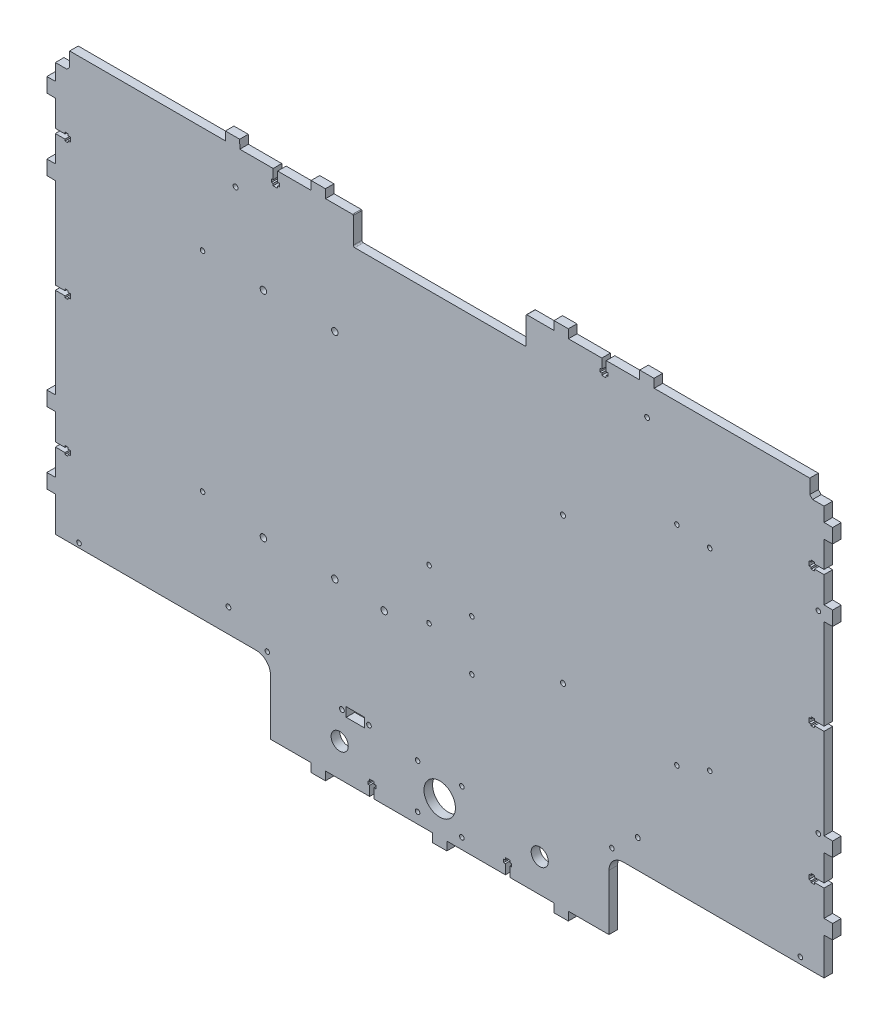
SolidWorks part; units mm, degrees
material "Клен"
ref_plane "Front" through (0, 0, 0) normal (0, 0, 1) x (1, 0, 0)
ref_plane "Top" through (0, 0, 0) normal (0, 1, 0) x (1, 0, 0)
ref_plane "Right" through (0, 0, 0) normal (1, 0, 0) x (0, 0, -1)
sketch "Эскиз1" plane through (0, 0, 0) normal (0, 0, 1) x (1, 0, 0)
  line L0 (89.7419, 500.1376) -> (118.0919, 500.1376)
  line L1 (118.0919, 500.1376) -> (118.1919, 494.1376)
  line L2 (118.1919, 494.1376) -> (128.1919, 494.1376)
  line L3 (128.1919, 494.1376) -> (128.2919, 500.1376)
  line L4 (128.2919, 500.1376) -> (159.1419, 500.1376)
  line L5 (159.1419, 500.1376) -> (159.1419, 506.9376)
  line L6 (159.1419, 506.9376) -> (157.9419, 506.9376)
  line L7 (157.9419, 506.9376) -> (157.9419, 509.1376)
  line L8 (157.9419, 509.1376) -> (159.1419, 509.1376)
  line L9 (159.1419, 509.1376) -> (159.1419, 510.6376)
  line L10 (159.1419, 510.6376) -> (162.2419, 510.6376)
  line L11 (162.2419, 510.6376) -> (162.2419, 509.1376)
  line L12 (162.2419, 509.1376) -> (163.4419, 509.1376)
  line L13 (163.4419, 509.1376) -> (163.4419, 506.9376)
  line L14 (163.4419, 506.9376) -> (162.2419, 506.9376)
  line L15 (162.2419, 506.9376) -> (162.2419, 500.1376)
  line L16 (-51.8081, 695.792) -> (-54.0081, 695.792)
  line L17 (-66.8081, 623.542) -> (-60.8081, 623.442)
  line L18 (162.2419, 500.1376) -> (203.0919, 500.1376)
  line L19 (203.0919, 500.1376) -> (203.1919, 494.1376)
  line L20 (203.1919, 494.1376) -> (213.1919, 494.1376)
  line L21 (213.1919, 494.1376) -> (213.2919, 500.1376)
  line L22 (213.2919, 500.1376) -> (254.1419, 500.1376)
  line L23 (254.1419, 500.1376) -> (254.1419, 506.9376)
  line L24 (254.1419, 506.9376) -> (252.9419, 506.9376)
  line L25 (252.9419, 506.9376) -> (252.9419, 509.1376)
  line L26 (252.9419, 509.1376) -> (254.1419, 509.1376)
  line L27 (254.1419, 509.1376) -> (254.1419, 510.6376)
  line L28 (254.1419, 510.6376) -> (257.2419, 510.6376)
  line L29 (257.2419, 510.6376) -> (257.2419, 509.1376)
  line L30 (257.2419, 509.1376) -> (258.4419, 509.1376)
  line L31 (258.4419, 509.1376) -> (258.4419, 506.9376)
  line L32 (258.4419, 506.9376) -> (257.2419, 506.9376)
  line L33 (257.2419, 506.9376) -> (257.2419, 500.1376)
  line L34 (257.2419, 500.1376) -> (288.0919, 500.1376)
  line L35 (288.0919, 500.1376) -> (288.1919, 494.1376)
  line L36 (288.1919, 494.1376) -> (298.1919, 494.1376)
  line L37 (298.1919, 494.1376) -> (298.2919, 500.1376)
  line L38 (298.2919, 500.1376) -> (326.6419, 500.1376)
  line L97 (367.1919, 847.1376) -> (358.2919, 847.1376)
  line L98 (358.2919, 847.1376) -> (358.1919, 853.1376)
  line L99 (358.1919, 853.1376) -> (348.1919, 853.1376)
  line L100 (348.1919, 853.1376) -> (348.0919, 847.1376)
  line L101 (348.0919, 847.1376) -> (324.7419, 847.1376)
  line L102 (324.7419, 847.1376) -> (324.7419, 840.3376)
  line L103 (324.7419, 840.3376) -> (325.9419, 840.3376)
  line L104 (325.9419, 840.3376) -> (325.9419, 838.1376)
  line L105 (325.9419, 838.1376) -> (324.7419, 838.1376)
  line L106 (324.7419, 838.1376) -> (324.7419, 836.6376)
  line L107 (324.7419, 836.6376) -> (321.6419, 836.6376)
  line L108 (321.6419, 836.6376) -> (321.6419, 838.1376)
  line L109 (321.6419, 838.1376) -> (320.4419, 838.1376)
  line L110 (320.4419, 838.1376) -> (320.4419, 840.3376)
  line L111 (320.4419, 840.3376) -> (321.6419, 840.3376)
  line L112 (321.6419, 840.3376) -> (321.6419, 847.1376)
  line L113 (321.6419, 847.1376) -> (298.2919, 847.1376)
  line L114 (298.2919, 847.1376) -> (298.1919, 853.1376)
  line L115 (298.1919, 853.1376) -> (288.1919, 853.1376)
  line L116 (288.1919, 853.1376) -> (288.0919, 847.1376)
  line L117 (288.0919, 847.1376) -> (269.1919, 847.1376)
  line L118 (268.6919, 846.6376) -> (268.6919, 828.542)
  line L119 (267.6919, 827.542) -> (148.6919, 827.542)
  line L120 (147.6919, 828.542) -> (147.6919, 846.542)
  line L121 (147.1919, 847.042) -> (128.2919, 847.042)
  line L122 (128.2919, 847.042) -> (128.1919, 853.042)
  line L123 (128.1919, 853.042) -> (118.1919, 853.042)
  line L124 (118.1919, 853.042) -> (118.0919, 847.042)
  line L125 (118.0919, 847.042) -> (94.7419, 847.042)
  line L126 (94.7419, 847.042) -> (94.7419, 840.242)
  line L127 (94.7419, 840.242) -> (95.9419, 840.242)
  line L128 (95.9419, 840.242) -> (95.9419, 838.042)
  line L129 (95.9419, 838.042) -> (94.7419, 838.042)
  line L130 (94.7419, 838.042) -> (94.7419, 836.542)
  line L131 (94.7419, 836.542) -> (91.6419, 836.542)
  line L132 (91.6419, 836.542) -> (91.6419, 838.042)
  line L133 (91.6419, 838.042) -> (90.4419, 838.042)
  line L134 (90.4419, 838.042) -> (90.4419, 840.242)
  line L135 (90.4419, 840.242) -> (91.6419, 840.242)
  line L136 (91.6419, 840.242) -> (91.6419, 847.042)
  line L137 (91.6419, 847.042) -> (68.2919, 847.042)
  line L138 (68.2919, 847.042) -> (68.1919, 853.042)
  line L139 (68.1919, 853.042) -> (58.1919, 853.042)
  line L140 (58.1919, 853.042) -> (58.0919, 847.042)
  line L141 (58.0919, 847.042) -> (49.1919, 847.042)
  line L199 (39.1919, 871.432) -> (39.1919, 501.6876) construction
  line L201 (142.7002, 546.3976) -> (155.7002, 546.3976)
  line L202 (155.7002, 546.3976) -> (155.7002, 539.8976)
  line L203 (155.7002, 539.8976) -> (142.7002, 539.8976)
  line L204 (142.7002, 539.8976) -> (142.7002, 546.3976)
  line L205 (-60.8081, 871.432) -> (-60.8081, 501.6876) construction
  line L206 (-50.3081, 791.992) -> (-51.8081, 791.992)
  line L207 (-60.8081, 696.992) -> (-60.8081, 633.642)
  line L208 (-60.8081, 795.092) -> (-54.0081, 795.092)
  line L209 (-51.8081, 791.992) -> (-51.8081, 790.792)
  line L210 (-54.0081, 700.092) -> (-54.0081, 701.292)
  line L211 (-51.8081, 700.092) -> (-50.3081, 700.092)
  line L212 (-60.8081, 835.042) -> (-60.8081, 823.642)
  line L213 (-51.8081, 795.092) -> (-50.3081, 795.092)
  line L214 (-54.0081, 701.292) -> (-51.8081, 701.292)
  line L215 (-50.3081, 696.992) -> (-51.8081, 696.992)
  line L216 (-54.0081, 601.992) -> (-60.8081, 601.992)
  line L217 (-60.8081, 773.642) -> (-66.8081, 773.542)
  line L218 (-50.3081, 601.992) -> (-51.8081, 601.992)
  line L219 (-60.8081, 813.442) -> (-60.8081, 795.092)
  line L220 (-54.0081, 795.092) -> (-54.0081, 796.292)
  line L221 (-54.0081, 796.292) -> (-51.8081, 796.292)
  line L222 (-51.8081, 696.992) -> (-51.8081, 695.792)
  line L223 (-54.0081, 606.292) -> (-51.8081, 606.292)
  line L224 (-60.8081, 573.442) -> (-60.8081, 549.042)
  line L225 (-52.8081, 835.042) -> (-60.8081, 835.042)
  line L226 (-54.0081, 790.792) -> (-54.0081, 791.992)
  line L227 (-51.8081, 605.092) -> (-50.3081, 605.092)
  line L228 (-66.8081, 583.542) -> (-66.8081, 573.542)
  line L229 (-51.8081, 790.792) -> (-54.0081, 790.792)
  line L230 (-54.0081, 605.092) -> (-54.0081, 606.292)
  line L231 (-51.8081, 601.992) -> (-51.8081, 600.792)
  line L232 (-66.8081, 823.542) -> (-66.8081, 813.542)
  line L233 (-50.3081, 795.092) -> (-50.3081, 791.992)
  line L234 (-60.8081, 633.642) -> (-66.8081, 633.542)
  line L235 (-60.8081, 583.642) -> (-66.8081, 583.542)
  line L236 (-66.8081, 813.542) -> (-60.8081, 813.442)
  line L237 (-66.8081, 773.542) -> (-66.8081, 763.542)
  line L238 (-51.8081, 600.792) -> (-54.0081, 600.792)
  line L239 (-66.8081, 763.542) -> (-60.8081, 763.442)
  line L240 (-50.3081, 700.092) -> (-50.3081, 696.992)
  line L241 (-60.8081, 623.442) -> (-60.8081, 605.092)
  line L243 (-54.0081, 791.992) -> (-60.8081, 791.992)
  line L244 (-54.0081, 695.792) -> (-54.0081, 696.992)
  line L245 (-60.8081, 823.642) -> (-66.8081, 823.542)
  line L246 (-51.8081, 796.292) -> (-51.8081, 795.092)
  line L247 (-51.8081, 701.292) -> (-51.8081, 700.092)
  line L248 (-60.8081, 601.992) -> (-60.8081, 583.642)
  line L249 (-54.0081, 696.992) -> (-60.8081, 696.992)
  line L250 (-66.8081, 633.542) -> (-66.8081, 623.542)
  line L251 (-60.8081, 763.442) -> (-60.8081, 700.092)
  line L252 (-54.0081, 600.792) -> (-54.0081, 601.992)
  line L254 (-50.8081, 847.042) -> (-50.8081, 837.042)
  line L255 (-50.8081, 837.042) -> (-52.8081, 835.042)
  line L256 (-60.8081, 700.092) -> (-54.0081, 700.092)
  line L257 (-60.8081, 605.092) -> (-54.0081, 605.092)
  line L258 (-50.3081, 605.092) -> (-50.3081, 601.992)
  line L259 (-60.8081, 791.992) -> (-60.8081, 773.642)
  line L260 (-51.8081, 606.292) -> (-51.8081, 605.092)
  line L261 (-66.8081, 573.542) -> (-60.8081, 573.442)
  line L263 (-50.8081, 847.042) -> (49.1919, 847.042)
  line L264 (377.1919, 871.432) -> (377.1919, 476.2445) construction
  line L265 (477.1919, 871.432) -> (477.1919, 476.2445) construction
  line L266 (477.1919, 625.0876) -> (483.1919, 625.1876)
  line L267 (466.6919, 698.6376) -> (466.6919, 701.7376)
  line L268 (477.1919, 549.1376) -> (477.1919, 575.0876)
  line L269 (470.3919, 701.7376) -> (477.1919, 701.7376)
  line L270 (477.1919, 585.2876) -> (477.1919, 603.6376)
  line L271 (477.1919, 796.7376) -> (477.1919, 815.0876)
  line L272 (477.1919, 575.0876) -> (483.1919, 575.1876)
  line L273 (468.1919, 603.6376) -> (466.6919, 603.6376)
  line L274 (477.1919, 635.2876) -> (477.1919, 698.6376)
  line L275 (470.3919, 792.4376) -> (468.1919, 792.4376)
  line L276 (467.1919, 837.1376) -> (467.1919, 847.1376)
  line L277 (483.1919, 635.1876) -> (477.1919, 635.2876)
  line L278 (468.1919, 796.7376) -> (468.1919, 797.9376)
  line L279 (483.1919, 585.1876) -> (477.1919, 585.2876)
  line L280 (468.1919, 698.6376) -> (466.6919, 698.6376)
  line L281 (468.1919, 793.6376) -> (466.6919, 793.6376)
  line L282 (469.1919, 835.1376) -> (467.1919, 837.1376)
  line L283 (483.1919, 575.1876) -> (483.1919, 585.1876)
  line L284 (470.3919, 603.6376) -> (470.3919, 602.4376)
  line L285 (470.3919, 697.4376) -> (468.1919, 697.4376)
  line L286 (477.1919, 701.7376) -> (477.1919, 765.0876)
  line L287 (477.1919, 793.6376) -> (470.3919, 793.6376)
  line L288 (483.1919, 815.1876) -> (483.1919, 825.1876)
  line L289 (470.3919, 606.7376) -> (477.1919, 606.7376)
  line L290 (470.3919, 698.6376) -> (470.3919, 697.4376)
  line L291 (483.1919, 775.1876) -> (477.1919, 775.2876)
  line L292 (466.6919, 603.6376) -> (466.6919, 606.7376)
  line L293 (466.6919, 793.6376) -> (466.6919, 796.7376)
  line L294 (470.3919, 797.9376) -> (470.3919, 796.7376)
  line L295 (477.1919, 825.2876) -> (477.1919, 835.1376)
  line L296 (470.3919, 602.4376) -> (468.1919, 602.4376)
  line L297 (483.1919, 625.1876) -> (483.1919, 635.1876)
  line L298 (468.1919, 697.4376) -> (468.1919, 698.6376)
  line L299 (470.3919, 702.9376) -> (470.3919, 701.7376)
  line L301 (468.1919, 607.9376) -> (470.3919, 607.9376)
  line L302 (470.3919, 793.6376) -> (470.3919, 792.4376)
  line L303 (466.6919, 796.7376) -> (468.1919, 796.7376)
  line L304 (477.1919, 603.6376) -> (470.3919, 603.6376)
  line L305 (477.1919, 606.7376) -> (477.1919, 625.0876)
  line L306 (477.1919, 775.2876) -> (477.1919, 793.6376)
  line L307 (468.1919, 792.4376) -> (468.1919, 793.6376)
  line L308 (477.1919, 815.0876) -> (483.1919, 815.1876)
  line L309 (466.6919, 606.7376) -> (468.1919, 606.7376)
  line L310 (468.1919, 606.7376) -> (468.1919, 607.9376)
  line L311 (466.6919, 701.7376) -> (468.1919, 701.7376)
  line L312 (468.1919, 702.9376) -> (470.3919, 702.9376)
  line L313 (468.1919, 797.9376) -> (470.3919, 797.9376)
  line L315 (470.3919, 607.9376) -> (470.3919, 606.7376)
  line L316 (477.1919, 698.6376) -> (470.3919, 698.6376)
  line L317 (468.1919, 701.7376) -> (468.1919, 702.9376)
  line L318 (477.1919, 765.0876) -> (483.1919, 765.1876)
  line L319 (470.3919, 796.7376) -> (477.1919, 796.7376)
  line L320 (468.1919, 602.4376) -> (468.1919, 603.6376)
  line L321 (483.1919, 765.1876) -> (483.1919, 775.1876)
  line L322 (483.1919, 825.1876) -> (477.1919, 825.2876)
  line L323 (477.1919, 835.1376) -> (469.1919, 835.1376)
  line L325 (367.1919, 847.1376) -> (467.1919, 847.1376)
  line L326 (336.6419, 549.1376) -> (377.1919, 549.1376)
  line L327 (326.6419, 500.1376) -> (326.6419, 539.1376)
  line L328 (377.1919, 549.1376) -> (477.1919, 549.1376)
  line L329 (89.7419, 539.042) -> (89.7419, 500.1376)
  line L330 (79.7419, 549.042) -> (39.1919, 549.042)
  line L331 (-60.8081, 549.042) -> (39.1919, 549.042)
  line L332 (208.1919, 486.1481) -> (208.1919, 880.8098) construction
  line L333 (107.749, 552.1376) -> (-66.0548, 552.1376) construction
  line L334 (315.5919, 553.6876) -> (489.3697, 553.6876) construction
  line L335 (87.5419, 557.9345) -> (87.5419, 540.5243) construction
  line L336 (328.7419, 492.2341) -> (328.7419, 562.4741) construction
  line L337 (42.1919, 871.432) -> (42.1919, 565.6434) construction
  line L338 (-84.499, 772.492) -> (54.9834, 772.492) construction
  line L339 (-84.499, 626.492) -> (54.9834, 626.492) construction
  circle A0 centre (138.1919, 523.1376) radius 6
  circle A1 centre (208.1919, 523.1376) radius 11
  circle A2 centre (278.1919, 523.1376) radius 6
  circle A3 centre (192.6919, 538.6376) radius 1.6
  circle A4 centre (223.6919, 538.6376) radius 1.6
  circle A5 centre (158.7002, 543.1376) radius 1.6265
  circle A6 centre (139.7002, 543.1376) radius 1.7
  circle A7 centre (192.6919, 507.6376) radius 1.6
  circle A8 centre (223.6919, 507.6376) radius 1.6
  circle A9 centre (65.2801, 822.6887) radius 1.7
  circle A10 centre (353.3431, 826.9394) radius 1.7
  circle A11 centre (84.7857, 769.7888) radius 2.25
  circle A12 centre (134.7857, 769.7888) radius 2.25
  circle A13 centre (294.4853, 738.3683) radius 1.75
  circle A15 centre (200.7177, 661.1578) radius 1.6
  circle A16 centre (230.7177, 645.1578) radius 1.6
  circle A17 centre (200.7177, 625.8978) radius 1.6
  circle A18 centre (84.7857, 619.7888) radius 2.25
  circle A19 centre (134.7857, 619.7888) radius 2.25
  circle A20 centre (169.2857, 617.7888) radius 2.25
  circle A21 centre (230.7177, 609.8978) radius 1.6
  circle A22 centre (294.4853, 636.3683) radius 1.75
  circle A24 centre (346.7847, 569.0716) radius 1.7
  circle A26 centre (60.3069, 565.6434) radius 1.7
  arc A30 (148.6919, 827.542) -> (147.6919, 828.542) centre (148.6919, 828.542) cw
  arc A31 (268.6919, 828.542) -> (267.6919, 827.542) centre (267.6919, 828.542) cw
  arc A32 (269.1919, 847.1376) -> (268.6919, 846.6376) centre (269.1919, 846.6376) ccw
  arc A33 (147.6919, 846.542) -> (147.1919, 847.042) centre (147.1919, 846.542) ccw
  arc A38 (326.6419, 539.1376) -> (336.6419, 549.1376) centre (336.6419, 539.1376) cw
  arc A39 (89.7419, 539.042) -> (79.7419, 549.042) centre (79.7419, 539.042) ccw
  circle A40 centre (-44.2581, 552.1376) radius 1.6
  circle A41 centre (460.6419, 553.6876) radius 1.6
  circle A46 centre (87.5419, 552.1376) radius 1.6
  circle A47 centre (328.7419, 553.6876) radius 1.6
  circle A48 centre (42.1919, 772.492) radius 1.6
  circle A49 centre (42.1919, 626.492) radius 1.6
  circle A50 centre (374.1919, 626.492) radius 1.6
  circle A51 centre (374.1919, 772.492) radius 1.6
  circle A52 centre (397.1919, 769.7505) radius 1.6
  circle A53 centre (473.1919, 769.7505) radius 1.6
  circle A54 centre (473.1919, 634.7505) radius 1.6
  circle A55 centre (397.1919, 634.7505) radius 1.6
  point P185 (0, 0)
  dimension "D1" = 12
  dimension "D2" = 22
  dimension "D3" = 12
  dimension "D4" = 169
  dimension "D5" = 1
  dimension "D6" = 0.5
  dimension "D10" = 3.2
  dimension "D12" = 3.2
  dimension "D13" = 16.55
  dimension "D14" = 48.35
  dimension "D15" = 3.2
  dimension "D17" = 3.2
  dimension "D21" = 3.2
  dimension "D22" = 3.2
  dimension "D24" = 23
  dimension "D26" = 31
  dimension "D27" = 31
  dimension "D28" = 31
  dimension "D30" = 23
  dimension "D32" = 43
  dimension "D33" = 43
  dimension "D34" = 3.2
  dimension "D35" = 3.2
  dimension "D36" = 3.2
  dimension "D37" = 3.2
  dimension "D7" = 100
  dimension "D8" = 100
  dimension "D9" = 169
  dimension "D11" = 16.55
  dimension "D16" = 48.45
  dimension "D18" = 3
  dimension "D19" = 74.55
  dimension "D20" = 146
  dimension "D23" = 23
  dimension "D25" = 7.5
  dimension "D29" = 7.5
  dimension "D31" = 39.76
extrude "Бобышка-Вытянуть1" add sketch "Эскиз1" along normal blind 6 contours L0 L1 L2 L3 L4 L5 L6 L7 L8 L9 L10 L11 L12 L13 L14 L15 L18 L19 L20 L21 L22 L23 L24 L25 L26 L27 L28 L29 L30 L31 L32 L33 L34 L35 L36 L37 L38 region at (208.2171, 684.8197, 0)
